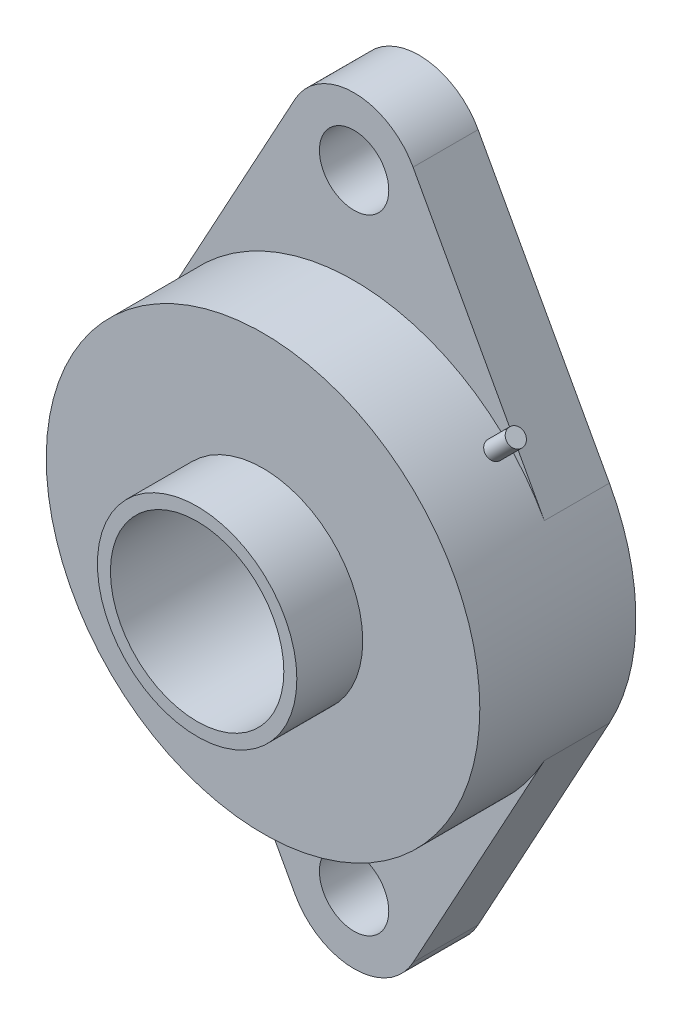
SolidWorks part; units mm, degrees
material "铸造合金钢"
ref_plane "前视" through (0, 0, 0) normal (0, 0, 1) x (1, 0, 0)
ref_plane "上视" through (0, 0, 0) normal (0, 1, 0) x (1, 0, 0)
ref_plane "右视" through (0, 0, 0) normal (1, 0, 0) x (0, 0, -1)
ref_axis "基准轴1" through (0, 0, -80.9) along (0, 0, 1)
ref_plane "基准面1" through (0, 0, 0) normal (-0.7071, 0.7071, 0) x (0, 0, 1)
sketch "草图1" plane through (0, 0, 0) normal (0, 0, 1) x (1, 0, 0)
  circle A0 centre (0, 0) radius 20
  circle A1 centre (0, 0) radius 23
  dimension "轴径" = 40
  dimension "壁厚" = 3
extrude "拉伸1" add sketch "草图1" along normal blind 51.2
sketch "草图2" plane through (0, 0, 0) normal (0, 0, 1) x (1, 0, 0)
  circle A0 centre (0, 0) radius 50
  circle A1 centre (0, 0) radius 23 construction
  circle A2 centre (0, 0) radius 23
  dimension "kd" = 100
extrude "拉伸2" add sketch "草图2" along normal blind 36
sketch "草图3" plane through (0, 0, 0) normal (0, 0, 1) x (1, 0, 0)
  line L1 (0, 72) -> (0, -72) construction
  line L2 (0, -50) -> (0, 50) construction
  line L3 (-43.8862, -23.9583) -> (-13.6047, -79.4271)
  line L4 (13.6047, -79.4271) -> (43.8862, -23.9583)
  line L5 (-13.6047, 79.4271) -> (-43.8862, 23.9583)
  line L6 (13.6047, 79.4271) -> (43.8862, 23.9583)
  arc A0 (13.6047, 79.4271) -> (-13.6047, 79.4271) centre (0, 72) ccw
  arc A1 (-13.6047, -79.4271) -> (13.6047, -79.4271) centre (0, -72) ccw
  circle A2 centre (0, 0) radius 50 construction
  arc A3 (-43.8862, -23.9583) -> (43.8862, -23.9583) centre (0, 0) ccw
  arc A4 (43.8862, 23.9583) -> (-43.8862, 23.9583) centre (0, 0) ccw
  point P7 (0, 87.5)
  point P8 (0, -87.5)
  dimension "最大外围" = 175
  dimension "lsjl" = 144
extrude "拉伸3" add sketch "草图3" along normal blind 15
sketch "草图4" plane through (0, 0, 0) normal (0, 0, 1) x (1, 0, 0)
  line L0 (0, 72) -> (0, -72) construction
  circle A0 centre (0, 72) radius 8
  circle A1 centre (0, -72) radius 8
  dimension "螺栓孔径" = 16
  dimension "lsjl" = 144
extrude "切除-拉伸1" cut sketch "草图4" along normal blind 15
sketch "草图5" plane through (0, 0, 0) normal (-0.7071, 0.7071, 0) x (0, 0, 1)
  line L0 (18, -991.5621) -> (18, 49008.4379) construction
  line L1 (0, -50) -> (0, 50) construction
  line L2 (-80.9, 0) -> (80.9, 0) construction
  line L3 (18, 57) -> (20, 57)
  line L4 (18, 57) -> (18, 47)
  line L5 (18, 47) -> (20, 47)
  line L6 (20, 57) -> (20, 47)
  dimension "D1" = 18
  dimension "D2" = 10
  dimension "D3" = 47
  dimension "D4" = 4
revolve "旋转1" add sketch "草图5" angle 360 about L0
sketch "草图6" plane through (0, 0, 0) normal (0, 0, -1) x (-1, 0, 0)
  circle A0 centre (0, 0) radius 30
  circle A1 centre (0, 0) radius 20 construction
  dimension "D1" = 10
extrude "切除-拉伸2" cut sketch "草图6" against normal blind 2
equation "\"D3@草图5\" = \"kd\" * 0.5 -3"
